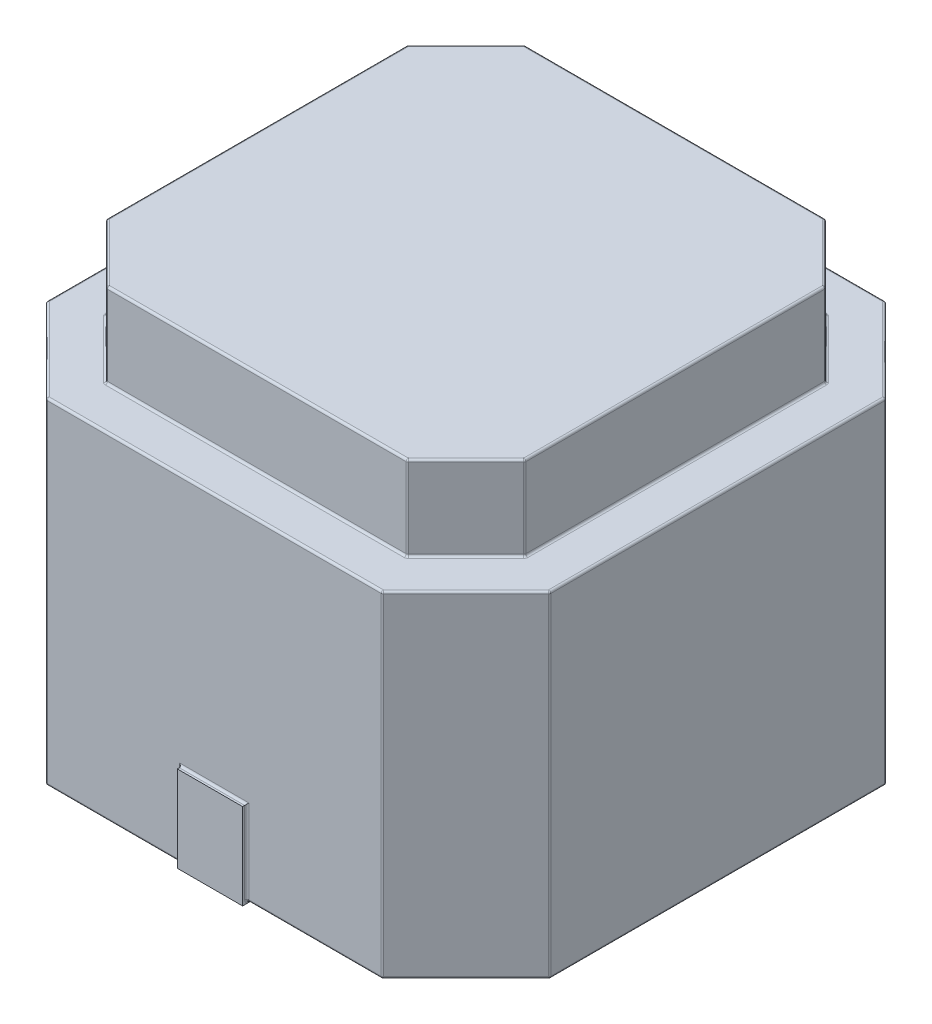
SolidWorks part; units mm, degrees
ref_plane "Front Plane" through (0, 0, 0) normal (0, 0, 1) x (1, 0, 0)
ref_plane "Top Plane" through (0, 0, 0) normal (0, 1, 0) x (1, 0, 0)
ref_plane "Right Plane" through (0, 0, 0) normal (1, 0, 0) x (0, 0, -1)
sketch "Sketch1" plane through (0, 0, 0) normal (0, 1, 0) x (1, 0, 0)
  line L0 (-3, 2) -> (-2, 3)
  line L1 (-2, 3) -> (2, 3)
  line L2 (-3, 2) -> (-3, -2)
  line L3 (-2, -3) -> (2, -3)
  line L4 (3, 2) -> (3, -2)
  line L5 (2, 3) -> (3, 2)
  line L6 (2, -3) -> (3, -2)
  line L7 (-3, -2) -> (-2, -3)
  point P0 (-3, 3)
  point P1 (3, -3)
  point P2 (-3, -3)
  point P3 (3, 3)
  dimension "D1" = 6
extrude "Boss-Extrude1" add sketch "Sketch1" along normal blind 5
sketch "Sketch2" plane through (0, 5, 0) normal (0, 1, 0) x (1, 0, 0)
  line L16 (2.492, 1.7896) -> (1.7896, 2.492)
  line L17 (1.7896, 2.492) -> (-1.7896, 2.492)
  line L18 (-1.7896, 2.492) -> (-2.492, 1.7896)
  line L19 (-2.492, 1.7896) -> (-2.492, -1.7896)
  line L20 (-2.492, -1.7896) -> (-1.7896, -2.492)
  line L21 (-1.7896, -2.492) -> (1.7896, -2.492)
  line L22 (1.7896, -2.492) -> (2.492, -1.7896)
  line L23 (2.492, -1.7896) -> (2.492, 1.7896)
  line L24 (2.492, 1.7896) -> (1.7896, 2.492)
  line L25 (1.7896, 2.492) -> (-1.7896, 2.492)
  line L26 (-1.7896, 2.492) -> (-2.492, 1.7896)
  line L27 (-2.492, 1.7896) -> (-2.492, -1.7896)
  line L28 (-2.492, -1.7896) -> (-1.7896, -2.492)
  line L29 (-1.7896, -2.492) -> (1.7896, -2.492)
  line L30 (1.7896, -2.492) -> (2.492, -1.7896)
  line L31 (2.492, -1.7896) -> (2.492, 1.7896)
  line M9 (3, 2) -> (2, 3)
  line M10 (2, 3) -> (-2, 3)
  line M11 (-2, 3) -> (-3, 2)
  line M12 (-3, 2) -> (-3, -2)
  line M13 (-3, -2) -> (-2, -3)
  line M14 (-2, -3) -> (2, -3)
  line M15 (2, -3) -> (3, -2)
  line M16 (3, -2) -> (3, 2)
  dimension "D1" = 0.508
extrude "Cut-Extrude1" cut sketch "Sketch2" against normal blind 1 contours L31 L30 L29 L28 L27 L26 L25 L24 M16 M9 M10 M11 M12 M13 M14 M15 region at (2.9151, 5, 0)
sketch "Sketch3" plane through (0, 0, 0) normal (0, -1, 0) x (1, 0, 0)
  line L0 (0, 1.3708) -> (0, -1.3708) construction
  line L1 (0.3886, 1.3708) -> (-0.3886, 1.3708)
  line L2 (0.3886, 1.3708) -> (0.3886, 3.05)
  line L3 (0.3886, 3.05) -> (-0.3886, 3.05)
  line L4 (-0.3886, 1.3708) -> (-0.3886, 3.05)
  line L5 (-0.3886, -1.3708) -> (0.3886, -1.3708)
  line L6 (-0.3886, -1.3708) -> (-0.3886, -3.05)
  line L7 (-0.3886, -3.05) -> (0.3886, -3.05)
  line L8 (2, -3) -> (3, -2)
  line L9 (3, -2) -> (3, 2)
  line L10 (3, 2) -> (2, 3)
  line L11 (2, 3) -> (-2, 3)
  line L12 (-2, 3) -> (-3, 2)
  line L13 (-3, 2) -> (-3, -2)
  line L14 (-3, -2) -> (-2, -3)
  line L15 (-2, -3) -> (2, -3)
  line L16 (2, -3) -> (3, -2)
  line L17 (3, -2) -> (3, 2)
  line L18 (3, 2) -> (2, 3)
  line L19 (2, 3) -> (-2, 3)
  line L20 (-2, 3) -> (-3, 2)
  line L21 (-3, 2) -> (-3, -2)
  line L22 (-3, -2) -> (-2, -3)
  line L23 (-2, -3) -> (2, -3)
  line L24 (0.3886, -1.3708) -> (0.3886, -3.05)
  point P16 (0, -1.3708)
  point P18 (0, 1.3708)
  line M21 (2, 3) -> (-2, 3)
  line M25 (-2, -3) -> (2, -3)
  dimension "D2" = 6.1
  dimension "D1" = 0
extrude "Boss-Extrude2" add sketch "Sketch3" against normal blind 1 and the other way blind 0.0254 contours L24 L5 L6 M25 | L4 L1 L2 M21 | L2 L1 L4 L3 | L6 L5 L24 L7 region at (0, 0, 2.1854) region at (0, 0, -2.1854)
fillet "Fillet1" radius 0.0254 62 edges at (0.3886, 0, 2.1854) (0.3886, 0, -2.1854) (0, 0, -1.3708) (-0.3886, 0, -2.1854) (-0.3886, 0, 2.1854) (0, 0, 1.3708) (1.7896, 4.5, -2.492) (2.492, 4.5, -1.7896) (2.492, 4.5, 1.7896) (1.7896, 4.5, 2.492) (-1.7896, 4.5, 2.492) (-2.492, 4.5, 1.7896) (-2.492, 4.5, -1.7896) (-1.7896, 4.5, -2.492) (0, 5, 2.492) (-2.1408, 5, 2.1408) (-2.492, 5, 0) (-2.1408, 5, -2.1408) (0, 5, -2.492) (2.1408, 5, -2.1408) (2.492, 5, 0) (2.1408, 5, 2.1408) (2.1408, 4, -2.1408) (0, 4, -2.492) (-2.1408, 4, -2.1408) (-2.492, 4, 0) (-2.1408, 4, 2.1408) (0, 4, 2.492) (2.1408, 4, 2.1408) (2.492, 4, 0) (0, 4, -3) (-1.1943, 0, -3) (-0.3886, 0.5, -3) (0, 1, -3) (0.3886, 0.5, -3) (1.1943, 0, -3) (-2.5, 0, -2.5) (-2, 2, -3) (-2.5, 4, -2.5) (-3, 0, 0) (-3, 2, -2) (-3, 4, 0) (-2.5, 0, 2.5) (-3, 2, 2) (-2.5, 4, 2.5) (-2, 2, 3) (0, 4, 3) (1.1943, 0, 3) (0.3886, 0.5, 3) (0, 1, 3) (-0.3886, 0.5, 3) (-1.1943, 0, 3) (2.5, 0, 2.5) (2, 2, 3) (2.5, 4, 2.5) (3, 0, 0) (3, 2, 2) (3, 4, 0) (2, 2, -3) (2.5, 0, -2.5) (3, 2, -2) (2.5, 4, -2.5)
